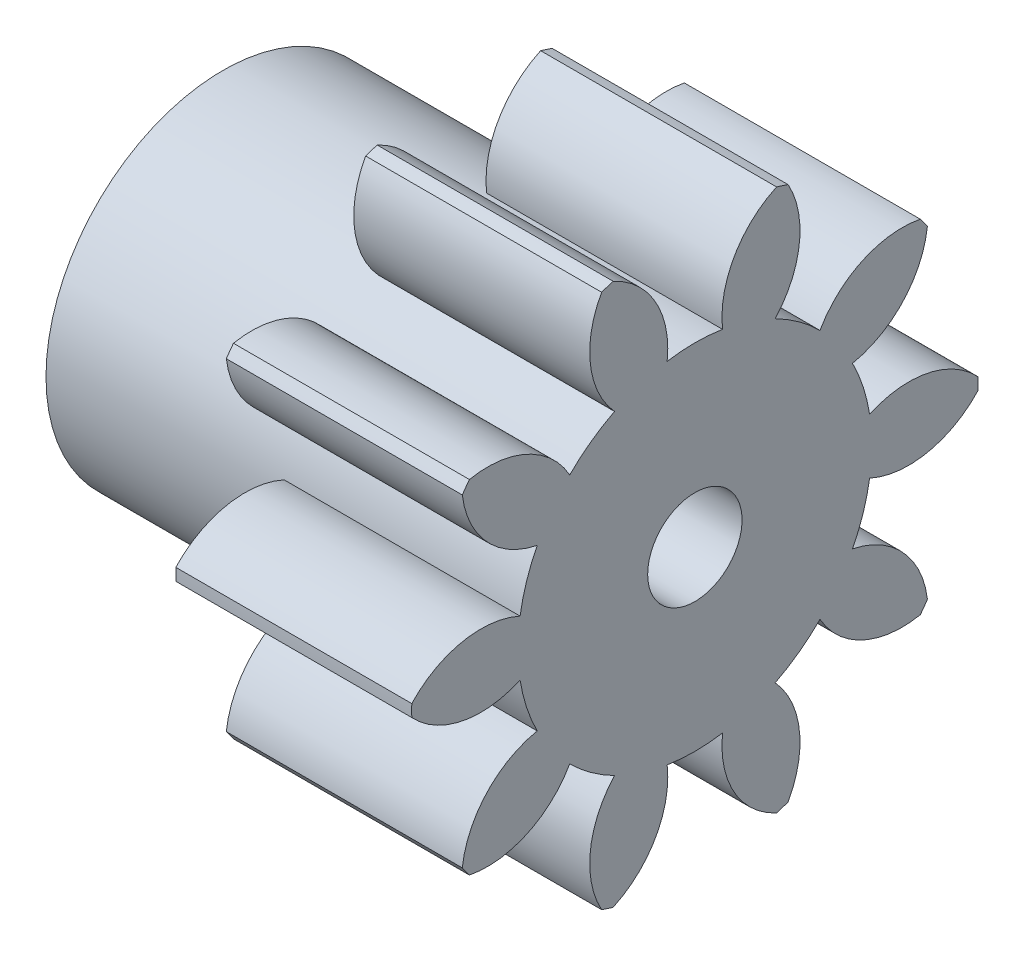
SolidWorks part; units mm, degrees
ref_plane "Plane1" through (0, 0, 0) normal (0, 0, 1) x (1, 0, 0)
ref_plane "Plane2" through (0, 0, 0) normal (0, 1, 0) x (1, 0, 0)
ref_plane "Plane3" through (0, 0, 0) normal (1, 0, 0) x (0, 0, -1)
sketch "HoldingSke" plane through (0, 0, 0) normal (0, 1, 0) x (1, 0, 0)
  line L0 (0, 0) -> (0.4924, -0.0868)
  line L1 (-15, 0) -> (100, 0) construction
  line L2 (0, 0) -> (-2.1039, 2.3779)
  line L3 (0, 0) -> (-11.863, 4.5341)
  line L4 (0, 0) -> (8.5048, 1.4996)
  line L5 (0, 0) -> (-18.7391, -6.9891)
  line L6 (0, 0) -> (-8.2896, -5.593)
  line L7 (-2.1039, 2.3779) -> (2.2011, 21.9091)
  line L8 (-76.2, 54.61) -> (-75.5, 54.61)
  line L9 (-71.009, 38.7566) -> (-53.1078, 45.2721)
  line L10 (-76.2, 71.12) -> (104.1128, 71.12)
  line L11 (0, 0) -> (-10, 0)
  line L12 (-76.2, 101.6) -> (-76.133, 101.6)
  line L13 (24.9733, 27.94) -> (52.9518, 28.4284)
  line L14 (24.9733, 27.94) -> (24.9743, 27.94)
  line L15 (24.9733, 27.94) -> (100.4006, 29.5858)
  line L16 (-63.627, -2) -> (-12.827, -2)
  circle A0 centre (0, 0) radius 2
  circle A1 centre (0, 0) radius 7.499
  circle A2 centre (0, 0) radius 25
  circle A3 centre (0, 0) radius 2
  dimension "MHD" = 14.998
  dimension "Hub_dia" = 50
  dimension "Bore" = 4
  dimension "MBD" = 4
  dimension "Num_teeth" = 10
  dimension "Pitch_radius" = 180.3128
  dimension "Pitch" = 0.5
  dimension "Width" = 10
  dimension "Overall_len" = 20
  dimension "Show_teeth" = 10
  dimension "Thickness" = 10
  dimension "OAL" = 20.0001
  dimension "T_dim" = 0.7
  dimension "Ap" = 20
  dimension "H" = 19.05
  dimension "Backlash" = 0.067
  dimension "Addendum_fac" = 1
  dimension "Dedendum_fac" = 1.25
  dimension "Clearance_fac" = 0.25
  dimension "Dedendum_add" = 0.001
  dimension "Module" = 2
sketch "BasProSke" plane through (0, 0, 0) normal (0, 1, 0) x (1, 0, 0)
  line L0 (-10, 0) -> (60, 0) construction
  line L1 (0, 0) -> (0, 12)
  line L2 (0, 0) -> (10, 0)
  line L3 (10, 0) -> (10, 12)
  line L4 (10, 12) -> (0, 12)
  dimension "Diameter" = 24
  dimension "Thickness" = 10
revolve "Base-Revolve" add sketch "BasProSke" angle 360 about L0
sketch "TooCutSke" plane through (0, 0, 0) normal (1, 0, 0) x (0, 0, -1)
  line L1 (0, 0) -> (0, 107) construction
  line L2 (0, 0) -> (-1.6814, 9.8576) construction
  line L3 (0, 0) -> (-6.1153, 18.8209) construction
  line L4 (-1.6814, 9.8576) -> (-3.0576, 9.4105) construction
  arc A0 (1.1737, 7.4066) -> (-1.1737, 7.4066) centre (0, 0) ccw
  arc A1 (3.4979, 11.5054) -> (-3.4979, 11.5054) centre (0, 0) ccw
  circle A2 centre (0, 0) radius 10 construction
  circle A3 centre (0, 0) radius 9.3969 construction
  arc A4 (-1.1737, 7.4066) -> (-3.4979, 11.5054) centre (-5.1477, 7.8615) ccw
  arc A5 (3.4979, 11.5054) -> (1.1737, 7.4066) centre (5.1477, 7.8615) ccw
  dimension "Root_dia" = 14.998
  dimension "Overcut_dia" = 24.0508
  dimension "Pitch_dia" = 20
  dimension "Base_dia" = 18.7939
  dimension "Flank_rad" = 4
  dimension "Half_ang" = 18
  dimension "Half_CT" = 1.4471
extrude "ToothCut" cut sketch "TooCutSke" along normal through all
fillet "Breaks" [suppressed] radius 0.04 tangent propagation no
fillet "RootFillets" [suppressed] radius 0.501
pattern_circular "TeethCuts" count 10 every 36 about axis through (-10, 0, 0) along (1, 0, 0) of "ToothCut", "RootFillets", "Breaks"
sketch "HubNeaOneSke" plane through (0, 0, 0) normal (-1, 0, 0) x (0, 0, 1)
  circle A0 centre (0, 0) radius 7.499
  dimension "Diameter" = 14.998
extrude "HubNearOne" add sketch "HubNeaOneSke" along normal blind 10.0001
sketch "HubNeaBotSke" plane through (0, 0, 0) normal (-1, 0, 0) x (0, 0, 1)
  circle A0 centre (0, 0) radius 7.499
  dimension "Diameter" = 14.998
extrude "HubNearBoth" [suppressed] add sketch "HubNeaBotSke" along normal blind 5
ref_plane "FarPln" through (10, 0, 0) normal (1, 0, 0) x (0, 0, -1)
sketch "HubFarSke" plane through (10, 0, 0) normal (1, 0, 0) x (0, 0, -1)
  circle A0 centre (0, 0) radius 7.499
  dimension "Diameter" = 14.998
extrude "HubFar" [suppressed] add sketch "HubFarSke" along normal blind 5
sketch "BorSke" plane through (0, 0, 0) normal (1, 0, 0) x (0, 0, -1)
  circle A0 centre (0, 0) radius 2
  dimension "Diameter" = 4
extrude "Bore" cut sketch "BorSke" along normal mid plane 40.0001
sketch "KeySke" plane through (0, 0, 0) normal (1, 0, 0) x (0, 0, -1)
  line L0 (-0.8, 0) -> (-0.8, 2.7)
  line L1 (-0.8, 2.7) -> (0.8, 2.7)
  line L2 (0.8, 2.7) -> (0.8, 0)
  line L3 (0, 0) -> (0, 34) construction
  line L4 (-0.8, 0) -> (0.8, 0)
  dimension "Offset" = 2.7
  dimension "Width" = 1.6
extrude "Keyway" [suppressed] cut sketch "KeySke" along normal mid plane 40.0001
pattern_circular "Keyway2" [suppressed] count 2 every 90 about axis through (-10, 0, 0) along (1, 0, 0)
equation "' \"Module@HoldingSke\" = 6.35"
equation "' \"Num_teeth@HoldingSke\" = 12"
equation "' \"Ap@HoldingSke\" =  20"
equation "' \"Width@HoldingSke\" = 0.5 * 25.4"
equation "' \"Hub_dia@HoldingSke\"= 1 * 25.4"
equation "' \"Overall_len@HoldingSke\" = 1.0 * 25.4"
equation "' \"Bore@HoldingSke\" = 0.75 * 25.4"
equation "' \"T_dim@HoldingSke\" = 0.1 * 25.4"
equation "' \"Width@KeySke\" = 0.25 * 25.4"
equation "' \"Show_teeth@HoldingSke\" = 13"
equation "' \"Backlash@HoldingSke\" = 0.009 * 25.4"
equation "' \"Addendum_fac@HoldingSke\" = 1.0"
equation "' \"Dedendum_fac@HoldingSke\" = 1.25"
equation "' \"Dedendum_add@HoldingSke\" = 0.00005 * 25.4"
equation "' \"Clearance_fac@HoldingSke\" = 0.25"
equation "\"Pitch@HoldingSke\" = 1 / \"Module@HoldingSke\""
equation "\"Overcut_dia@TooCutSke\" = (\"Num_teeth@HoldingSke\" + 2 * \"Addendum_fac@HoldingSke\") / \"Pitch@HoldingSke\" + 0.002 * 25.4"
equation "\"Pitch_dia@TooCutSke\" = \"Num_teeth@HoldingSke\" / \"Pitch@HoldingSke\""
equation "\"Base_dia@TooCutSke\" = \"Num_teeth@HoldingSke\" / \"Pitch@HoldingSke\" * cos((\"Ap@HoldingSke\"  * 3.14159265 / 180))"
equation "\"Root_dia@TooCutSke\" = (\"Num_teeth@HoldingSke\" + 2) / \"Pitch@HoldingSke\" - 2 * (\"Addendum_fac@HoldingSke\" + \"Dedendum_fac@HoldingSke\") / \"Pitch@HoldingSke\" - \"Dedendum_add@HoldingSke\" * 2"
equation "\"Half_ang@TooCutSke\" = 180 / \"Num_teeth@HoldingSke\""
equation "\"Half_CT@TooCutSke\" = \"Num_teeth@HoldingSke\" / \"Pitch@HoldingSke\" * sin((3.14159265 / 2 / \"Num_teeth@HoldingSke\")) / 2 - 7 * \"Backlash@HoldingSke\" / 4"
equation "\"Flank_rad@TooCutSke\" = \"Num_teeth@HoldingSke\" / \"Pitch@HoldingSke\" / 5"
equation "\"Radius@RootFillets\" = \"Clearance_fac@HoldingSke\" / \"Pitch@HoldingSke\" + \"Dedendum_add@HoldingSke\""
equation "\"Break_rad@Breaks\" = 0.02 / \"Pitch@HoldingSke\""
equation "\"Thickness@HoldingSke\" = \"Width@HoldingSke\""
equation "\"OAL@HoldingSke\" = \"Thickness@HoldingSke\""
equation "\"MHD@HoldingSke\" = (\"Num_teeth@HoldingSke\" + 2) / \"Pitch@HoldingSke\" - 2 * (\"Addendum_fac@HoldingSke\" + \"Dedendum_fac@HoldingSke\")  / \"Pitch@HoldingSke\" - \"Dedendum_add@HoldingSke\" * 2"
equation "\"MBD@HoldingSke\" = (\"Num_teeth@HoldingSke\" + 2) / \"Pitch@HoldingSke\" - 2 * (\"Addendum_fac@HoldingSke\" + \"Dedendum_fac@HoldingSke\")  / \"Pitch@HoldingSke\" - \"Dedendum_add@HoldingSke\" * 2 - 0.002 * 25.4"
equation "\"MHD@HoldingSke\" = ((sgn( \"MHD@HoldingSke\" - \"Hub_dia@HoldingSke\" )-1)*( \"MHD@HoldingSke\" - \"Hub_dia@HoldingSke\" ))/-2+ \"Hub_dia@HoldingSke\""
equation "\"MBD@HoldingSke\" = ((sgn( \"MBD@HoldingSke\" - \"Bore@HoldingSke\" )-1)*( \"MBD@HoldingSke\" - \"Bore@HoldingSke\" ))/-2+ \"Bore@HoldingSke\""
equation "\"OAL@HoldingSke\" = ((sgn( \"OAL@HoldingSke\" - \"Overall_len@HoldingSke\" )+1)*( \"OAL@HoldingSke\" - \"Overall_len@HoldingSke\" ))/2 + \"Overall_len@HoldingSke\" + 0.000002 * 25.4"
equation "\"Num_teeth@TeethCuts\" = int( \"Show_teeth@HoldingSke\" ) + 1"
equation "\"Num_teeth@TeethCuts\" = ((sgn( \"Num_teeth@TeethCuts\" - \"Num_teeth@HoldingSke\" )-1)*( \"Num_teeth@TeethCuts\" - \"Num_teeth@HoldingSke\" ))/-2+ \"Num_teeth@HoldingSke\""
equation "\"Num_teeth@TeethCuts\" = ((sgn( \"Num_teeth@TeethCuts\" - 2.0)+1)*( \"Num_teeth@TeethCuts\" - 2.0))/2 +2.0"
equation "\"Angle@TeethCuts\" = 360.0 / \"Num_teeth@HoldingSke\""
equation "\"Diameter@BasProSke\" = (\"Num_teeth@HoldingSke\" + 2 * \"Addendum_fac@HoldingSke\") / \"Pitch@HoldingSke\""
equation "\"Thickness@BasProSke\"  = \"Thickness@HoldingSke\""
equation "' \"Fillet_rad@BasProSke\" =  \"Thickness@HoldingSke\" * 0.05"
equation "\"MHD@HoldingSke\" = ((sgn( \"MHD@HoldingSke\" - \"Root_dia@TooCutSke\" )-1)*( \"MHD@HoldingSke\" - \"Root_dia@TooCutSke\" ))/-2+ \"Root_dia@TooCutSke\""
equation "\"Diameter@HubNeaOneSke\" = \"MHD@HoldingSke\""
equation "\"Length@HubNearOne\" = \"OAL@HoldingSke\" - \"Thickness@BasProSke\""
equation "\"Diameter@HubNeaBotSke\" = \"MHD@HoldingSke\""
equation "\"Length@HubNearBoth\" = ( \"OAL@HoldingSke\" - \"Thickness@BasProSke\" ) / 2.0"
equation "\"Thickness@FarPln\" = \"Thickness@BasProSke\""
equation "\"Diameter@HubFarSke\" = \"MHD@HoldingSke\""
equation "\"Length@HubFar\" = ( \"OAL@HoldingSke\" - \"Thickness@BasProSke\" ) / 2.0"
equation "\"Diameter@BorSke\" = \"MBD@HoldingSke\""
equation "\"D1@Bore\" = \"OAL@HoldingSke\" * 2.0"
equation "\"D1@Keyway\" = \"OAL@HoldingSke\" * 2.0"
equation "\"Offset@KeySke\" = \"T_dim@HoldingSke\" + \"MBD@HoldingSke\" / 2.0"
